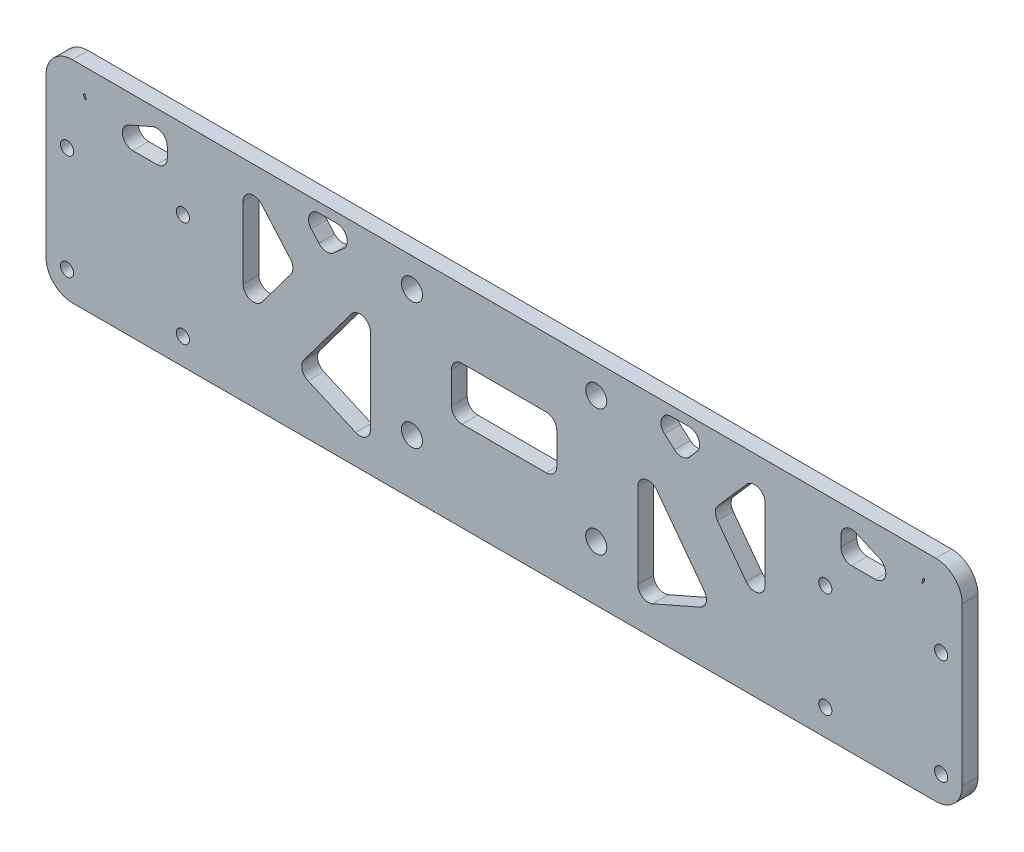
SolidWorks part; units mm, degrees
material "Thornel Mat VMA"
ref_plane "前视基准面" through (0, 0, 0) normal (0, 0, 1) x (1, 0, 0)
ref_plane "上视基准面" through (0, 0, 0) normal (0, 1, 0) x (1, 0, 0)
ref_plane "右视基准面" through (0, 0, 0) normal (1, 0, 0) x (0, 0, -1)
other "Configuration Table"
sketch "草图1" plane through (0, 0, 0) normal (0, 0, 1) x (1, 0, 0)
  line L0 (87, 0) -> (87, -45) construction
  line L1 (0, 0) -> (174, 0)
  line L2 (0, 0) -> (0, -45)
  line L3 (0, -45) -> (174, -45)
  line L4 (174, 0) -> (174, -45)
  line L5 (0, -22.5) -> (174, -22.5) construction
  circle A0 centre (69.5, -10.5) radius 2
  circle A1 centre (104.5, -10.5) radius 2
  circle A2 centre (69.5, -34.5) radius 2
  circle A3 centre (104.5, -34.5) radius 2
  dimension "D3" = 4
  dimension "D4" = 12
  dimension "D5" = 17.5
  dimension "D1" = 174
  dimension "D2" = 45
extrude "凸台-拉伸1" add sketch "草图1" along normal blind 3
sketch "草图2" plane through (0, 0, 3) normal (0, 0, 1) x (1, 0, 0)
  line L0 (87, 0) -> (87, -118.0863) construction
  line L1 (174, 0) -> (0, 0) construction
  line L2 (0, -45) -> (174, -45) construction
  line L4 (15, 4.2756) -> (15, -54.352) construction
  circle A0 centre (148, -20) radius 1.25
  circle A1 centre (148, -40) radius 1.25
  circle A2 centre (26, -40) radius 1.25
  circle A3 centre (26, -20) radius 1.25
  circle A4 centre (4, -20) radius 1.25
  circle A5 centre (4, -40) radius 1.25
  circle A6 centre (170, -40) radius 1.25
  circle A7 centre (170, -20) radius 1.25
  dimension "D1" = 2.5
  dimension "D3" = 5
  dimension "D5" = 11
  dimension "D4" = 166
  dimension "D2" = 2
extrude "切除-拉伸1" cut sketch "草图2" against normal blind 3
sketch "草图3" plane through (0, 0, 3) normal (0, 0, 1) x (1, 0, 0)
  line L0 (6.9646, -8.4465) -> (15.1518, -8.4465)
  line L1 (15.1518, -8.4465) -> (6.9646, -12.0373)
  line L2 (6.9646, -12.0373) -> (6.9646, -8.4465)
  line L3 (6.9646, -14.2202) -> (23.0317, -7.1732)
  line L4 (23.0317, -7.1732) -> (23.0317, -14.2202)
  line L5 (23.0317, -14.2202) -> (6.9646, -14.2202)
  line L6 (37.4157, -6.7984) -> (47.4569, -18.2585)
  line L7 (47.4569, -18.2585) -> (37.4157, -31.6832)
  line L8 (37.4157, -31.6832) -> (37.4157, -6.7984)
  line L9 (47.4569, -6.7984) -> (53.1373, -13.2815)
  line L10 (53.1373, -13.2815) -> (60.5364, -6.7984)
  line L11 (60.5364, -6.7984) -> (47.4569, -6.7984)
  line L12 (47.4569, -34.4118) -> (61.6109, -15.4886)
  line L13 (61.6109, -15.4886) -> (61.6109, -40.633)
  line L14 (61.6109, -40.633) -> (47.4569, -34.4118)
  line L15 (87, 0) -> (87, -71.8481) construction
  line L16 (174, 0) -> (0, 0) construction
  line L17 (112.3891, -40.633) -> (126.5431, -34.4118)
  line L18 (112.3891, -15.4886) -> (112.3891, -40.633)
  line L19 (126.5431, -34.4118) -> (112.3891, -15.4886)
  line L20 (113.4636, -6.7984) -> (126.5431, -6.7984)
  line L21 (120.8627, -13.2815) -> (113.4636, -6.7984)
  line L22 (126.5431, -6.7984) -> (120.8627, -13.2815)
  line L23 (136.5843, -31.6832) -> (136.5843, -6.7984)
  line L24 (126.5431, -18.2585) -> (136.5843, -31.6832)
  line L25 (136.5843, -6.7984) -> (126.5431, -18.2585)
  line L26 (150.9683, -14.2202) -> (167.0354, -14.2202)
  line L27 (150.9683, -7.1732) -> (150.9683, -14.2202)
  line L28 (167.0354, -14.2202) -> (150.9683, -7.1732)
  line L29 (167.0354, -12.0373) -> (167.0354, -8.4465)
  line L30 (158.8482, -8.4465) -> (167.0354, -12.0373)
  line L31 (167.0354, -8.4465) -> (158.8482, -8.4465)
  line L33 (77, -27.9501) -> (97, -27.9501)
  line L34 (77, -27.9501) -> (77, -17.9501)
  line L35 (77, -17.9501) -> (97, -17.9501)
  line L36 (97, -27.9501) -> (97, -17.9501)
  line L37 (77, -27.9501) -> (97, -17.9501) construction
  line L38 (77, -17.9501) -> (97, -27.9501) construction
  point P34 (87, -22.9501)
  dimension "D1" = 10
  dimension "D2" = 20
extrude "切除-拉伸2" cut sketch "草图3" against normal blind 4
fillet "圆角1" radius 2 34 edges at (15.1518, -8.4465, 1.5) (6.9646, -12.0373, 1.5) (6.9646, -8.4465, 1.5) (77, -27.9501, 1.5) (77, -17.9501, 1.5) (97, -17.9501, 1.5) (97, -27.9501, 1.5) (167.0354, -8.4465, 1.5) (167.0354, -12.0373, 1.5) (158.8482, -8.4465, 1.5) (126.5431, -34.4118, 1.5) (112.3891, -40.633, 1.5) (112.3891, -15.4886, 1.5) (126.5431, -6.7984, 1.5) (120.8627, -13.2815, 1.5) (113.4636, -6.7984, 1.5) (136.5843, -6.7984, 1.5) (136.5843, -31.6832, 1.5) (167.0354, -14.2202, 1.5) (150.9683, -14.2202, 1.5) (150.9683, -7.1732, 1.5) (23.0317, -7.1732, 1.5) (23.0317, -14.2202, 1.5) (6.9646, -14.2202, 1.5) (47.4569, -18.2585, 1.5) (37.4157, -31.6832, 1.5) (37.4157, -6.7984, 1.5) (53.1373, -13.2815, 1.5) (47.4569, -6.7984, 1.5) (60.5364, -6.7984, 1.5) (61.6109, -15.4886, 1.5) (61.6109, -40.633, 1.5) (47.4569, -34.4118, 1.5) (126.5431, -18.2585, 1.5)
fillet "圆角2" radius 5 4 edges at (0, 0, 1.5) (174, -45, 1.5) (0, -45, 1.5) (174, 0, 1.5)
sketch "草图4" plane through (0, 0, 3) normal (0, 0, 1) x (1, 0, 0)
  line L0 (174, -40) -> (174, -5) construction
  line L1 (174, -5) -> (80.7642, -5)
  line L2 (174, -5) -> (174, 0)
  line L3 (174, 0) -> (80.7642, 0)
  line L4 (80.7642, -5) -> (80.7642, 0)
  line L5 (169, 0) -> (5, 0) construction
  line L6 (87, 0) -> (87, -81.5728) construction
  line L7 (93.2358, -5) -> (93.2358, 0)
  line L8 (0, 0) -> (93.2358, 0)
  line L9 (0, -5) -> (93.2358, -5)
  line L10 (93.2358, -5) -> (93.2358, 0)
  line L11 (0, 0) -> (93.2358, 0)
  line L12 (0, -5) -> (0, 0)
  line L13 (0, -5) -> (93.2358, -5)
  dimension "D1" = 5
extrude "切除-拉伸3" cut sketch "草图4" against normal blind 4 contours L4 L1 L2 L3 | L12 L9 L7 L8 | L3 L4 L1 L2 region at (133.6179, -2.5, 3) region at (40.3821, -2.5, 3)
fillet "圆角3" radius 5 2 edges at (0, -5, 1.5) (174, -5, 1.5)
